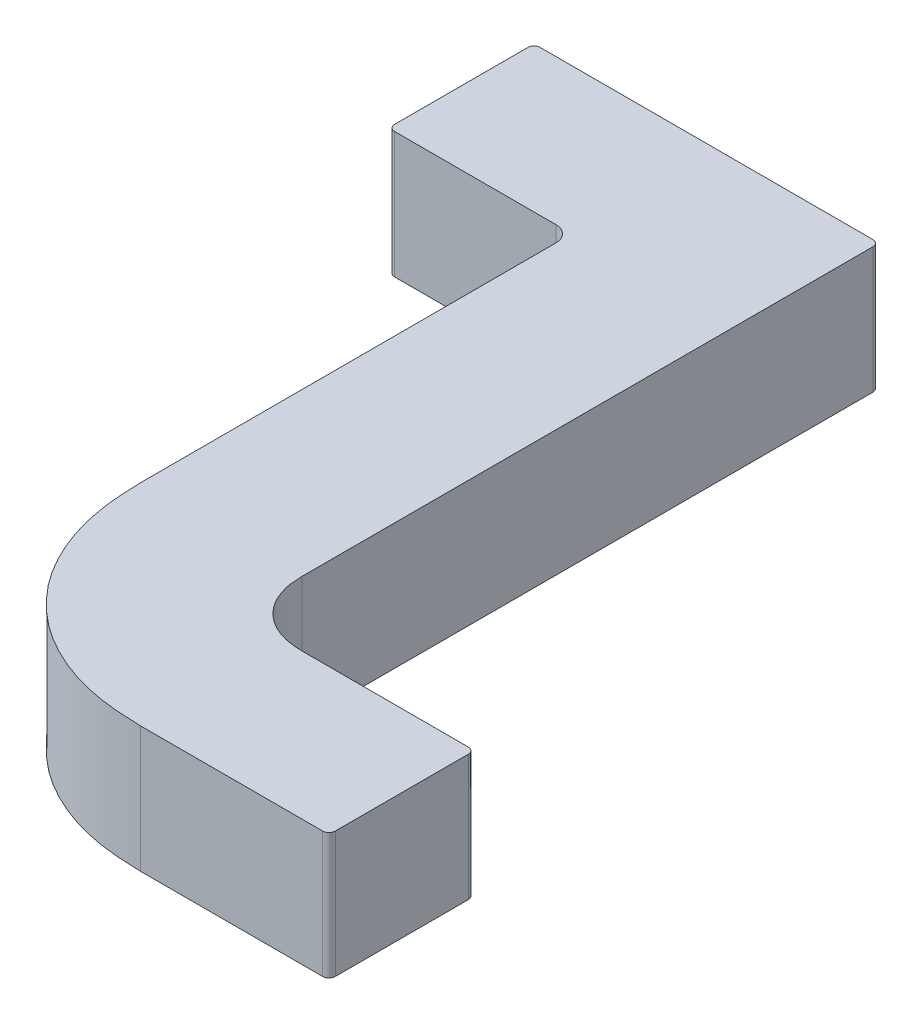
SolidWorks part; units mm, degrees
ref_plane "Front Plane" through (0, 0, 0) normal (0, 0, 1) x (1, 0, 0)
ref_plane "Top Plane" through (0, 0, 0) normal (0, 1, 0) x (1, 0, 0)
ref_plane "Right Plane" through (0, 0, 0) normal (1, 0, 0) x (0, 0, -1)
sketch "Sketch1" plane through (0, 0, 0) normal (0, 1, 0) x (1, 0, 0)
  text T0 "l" font "JetBrains Mono ExtraBold" height 125
extrude "Boss-Extrude1" add sketch "Sketch1" against normal blind 20
fillet "Fillet1" radius 2.5 1 edges at (33.3928, -10, -101.8876)
fillet "Fillet2" radius 1 5 edges at (4.2856, -10, -125) (4.2856, -10, -101.8876) (59.0815, -10, -125) (96.735, -10, 0) (96.735, -10, -23.1124)
